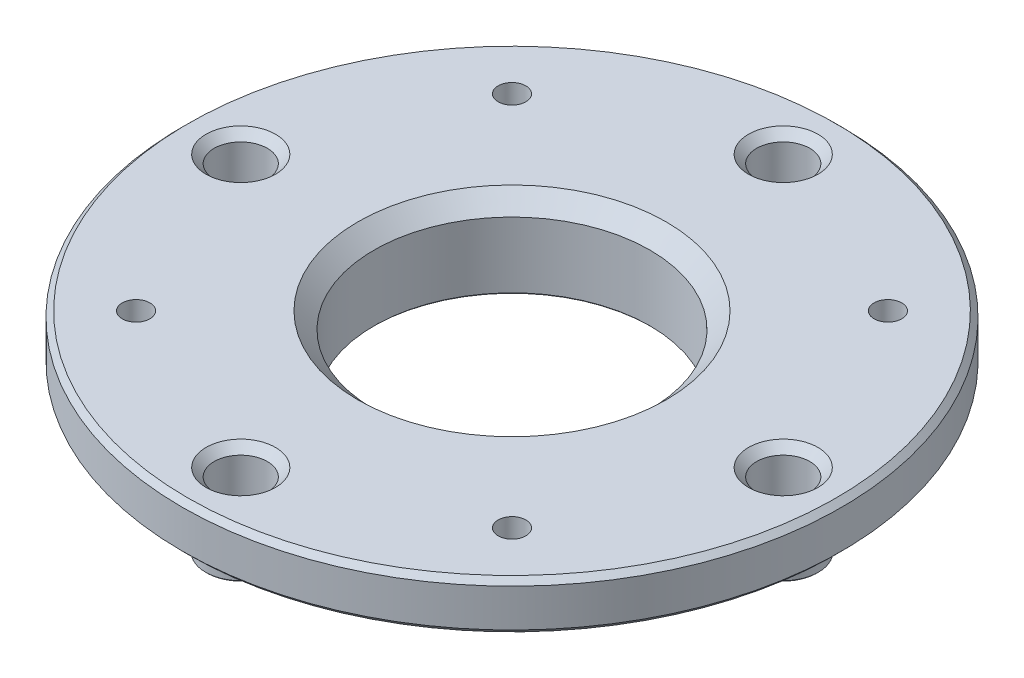
SolidWorks part; units mm, degrees
ref_plane "Front Plane" through (0, 0, 0) normal (0, 0, 1) x (1, 0, 0)
ref_plane "Top Plane" through (0, 0, 0) normal (0, 1, 0) x (1, 0, 0)
ref_plane "Right Plane" through (0, 0, 0) normal (1, 0, 0) x (0, 0, -1)
sketch "Sketch1" plane through (0, 0, 0) normal (0, 1, 0) x (1, 0, 0)
  line L0 (0, 0) -> (50, 0) construction
  line L1 (0, 0) -> (0, 50) construction
  line L2 (0, 0) -> (-50, 0) construction
  circle A0 centre (0, 0) radius 60.75
  circle A1 centre (0, 50) radius 4.9022
  circle A2 centre (50, 0) radius 4.9022
  circle A3 centre (0, -50) radius 4.9022
  circle A4 centre (-50, 0) radius 4.9022
  circle A5 centre (0, 0) radius 25.425
  point P14 (0, 0)
  dimension "D1" = 121.5
  dimension "D2" = 9.8044
  dimension "D4" = 50.85
  dimension "D5" = 50
  dimension "D3" = 4
extrude "Boss-Extrude1" add sketch "Sketch1" along normal blind 9
sketch "Sketch2" plane through (0, 0, 0) normal (0, -1, 0) x (1, 0, 0)
  circle A0 centre (0, 0) radius 25.425
  circle A1 centre (0, 0) radius 28.485
  circle A2 centre (0, 0) radius 25.425 construction
  dimension "D1" = 56.97
extrude "Boss-Extrude2" add sketch "Sketch2" along normal blind 6.35
chamfer "Chamfer1" distance 3 angle 45 1 edges at (0, 9, 25.425)
chamfer "Chamfer2" distance 1.5 angle 45 4 edges at (-50, 9, 4.9022) (0, 9, 54.9022) (50, 9, 4.9022) (0, 9, -45.0978)
chamfer "Chamfer3" distance 1 angle 45 2 edges at (0, 9, 60.75) (0, 0, 60.75)
sketch "Sketch3" plane through (0, 0, 0) normal (0, -1, 0) x (1, 0, 0)
  circle A0 centre (-50, 0) radius 4.9022 construction
  circle A1 centre (0, 50) radius 4.9022 construction
  circle A3 centre (50, 0) radius 4.9022 construction
  circle A4 centre (0, -50) radius 4.9022 construction
  circle A5 centre (-50, 0) radius 4.9022
  circle A6 centre (0, 50) radius 4.9022
  circle A7 centre (50, 0) radius 4.9022
  circle A8 centre (0, -50) radius 4.9022
  circle A9 centre (50, 0) radius 6.475
  circle A10 centre (0, -50) radius 6.475
  circle A11 centre (-50, 0) radius 6.475
  circle A12 centre (0, 50) radius 6.475
  dimension "D1" = 12.95
extrude "Boss-Extrude3" add sketch "Sketch3" along normal blind 4.75
chamfer "Chamfer4" distance 0.25 angle 45 9 edges at (0, -4.75, 45.0978) (0, -4.75, 43.525) (50, -4.75, -4.9022) (50, -4.75, -6.475) (0, -4.75, -54.9022) (0, -4.75, -56.475) (-50, -4.75, -4.9022) (-50, -4.75, -6.475) (0, -6.35, -25.425)
sketch "Sketch5" plane through (0, 0, 0) normal (0, -1, 0) x (1, 0, 0)
  line L0 (0, 0) -> (34.6482, -34.6482) construction
  line L1 (0, 0) -> (0, -50) construction
  line L2 (0, 0) -> (-34.6482, -34.6482) construction
  line L3 (0, 0) -> (-34.6482, 34.6482) construction
  line L4 (0, 0) -> (34.6482, 34.6482) construction
  point P11 (0, 0)
  dimension "D1" = 45
  dimension "D3" = 98
  dimension "D2" = 4
hole_wizard "Tap Drill for 1/4-20 Tap1" positions "Sketch6" profile "Sketch8" hole size "1/4-20" standard "ANSI Inch" end condition through all
sketch "Sketch6" plane through (0, 0, 0) normal (0, -1, 0) x (-1, 0, 0)
  line L0 (0, 0) -> (34.6482, -34.6482) construction
  point P0 (-34.6482, -34.6482)
  point P3 (-34.6482, 34.6482)
  point P6 (34.6482, 34.6482)
  point P9 (34.6482, -34.6482)
sketch "Sketch8" plane through (34.6482, 0, 34.6482) normal (1, 0, 0) x (0, 0, -1)
  line L0 (0, 0) -> (0, 9)
  line L1 (0, 9) -> (2.5527, 9)
  line L2 (2.5527, 9) -> (2.5527, 0)
  line L5 (2.5527, 0) -> (0, 0)
  line L11 (0, -6.35) -> (0, 107.95) construction
  dimension "Thru Hole Dia." = 5.1054
  dimension "Thru Hole Depth" = 9
chamfer "Chamfer6" distance 1 angle 45 1 edges at (0, -6.35, -28.485)
